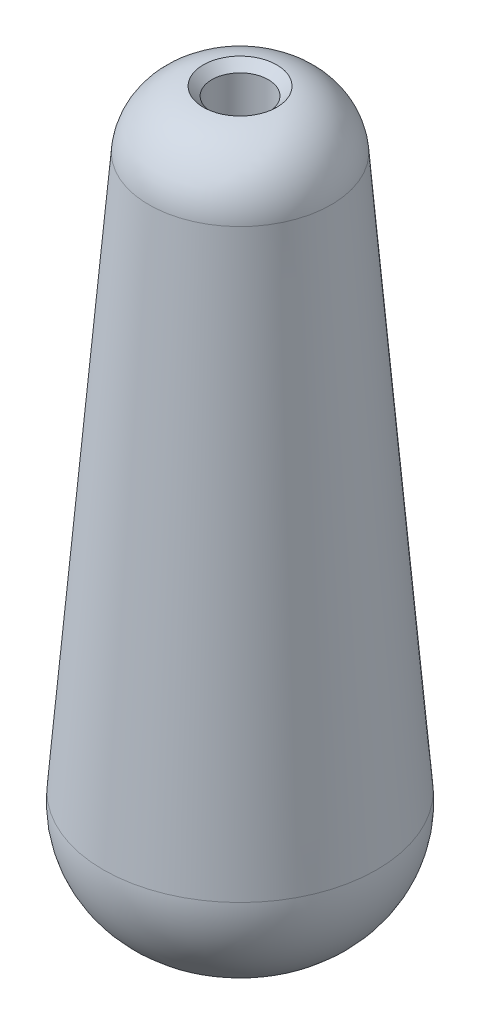
SolidWorks part; units mm, degrees
ref_plane "Front" through (0, 0, 0) normal (0, 0, 1) x (1, 0, 0)
ref_plane "Top" through (0, 0, 0) normal (0, 1, 0) x (1, 0, 0)
ref_plane "Right" through (0, 0, 0) normal (1, 0, 0) x (0, 0, -1)
sketch "Esquisse1" plane through (0, 0, 0) normal (0, 0, 1) x (1, 0, 0)
  line L0 (0, 0) -> (0, 80) construction
  line L1 (3.1, 0) -> (3.1, 80) construction
  line L2 (15, 12.9201) -> (10, 73.6448)
  line L3 (3.1, 0) -> (0, 0)
  line L4 (0, 0) -> (0, 4)
  line L5 (0, 4) -> (3.1, 4)
  line L6 (3.1, 4) -> (3.1, 80)
  arc A0 (3.1, 0) -> (15, 12.9201) centre (3.1, 11.9403) ccw
  arc A1 (10, 73.6448) -> (3.1, 80) centre (3.1, 73.0766) ccw
  dimension "D3" = 30
  dimension "D1" = 80
  dimension "D2" = 3.1
  dimension "D4" = 20
  dimension "D5" = 4
revolve "Révolution1" add sketch "Esquisse1" angle 360 about L0
chamfer "Chanfrein1" distance 1 angle 45 1 edges at (0, 80, -3.1)
